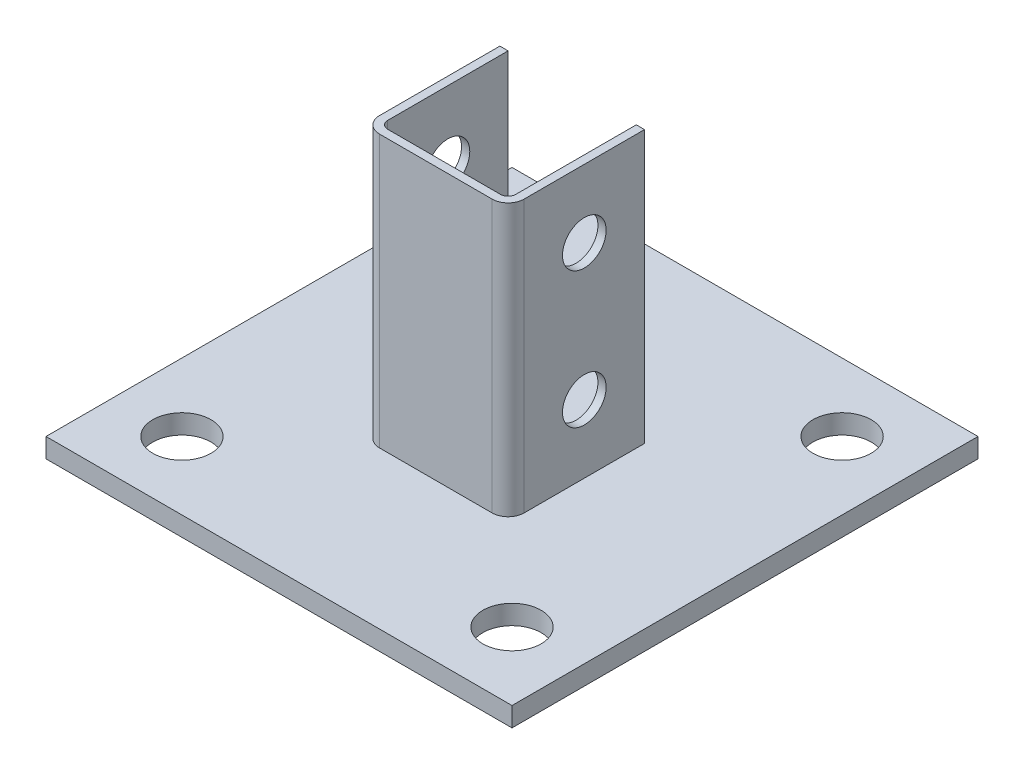
SolidWorks part; units mm, degrees
material "AISI Type 316L stainless steel"
ref_plane "Front Plane" through (0, 0, 0) normal (0, 0, 1) x (1, 0, 0)
ref_plane "Top Plane" through (0, 0, 0) normal (0, 1, 0) x (1, 0, 0)
ref_plane "Right Plane" through (0, 0, 0) normal (1, 0, 0) x (0, 0, -1)
ref_axis "X Axis" through (-125.9796, 0, 0) along (1, 0, 0)
ref_axis "Y Axis" through (0, -78.5041, 0) along (0, 1, 0)
ref_axis "Z Axis" through (0, 0, -88.99) along (0, 0, 1)
sketch "Sketch1" plane through (0, 0, 0) normal (0, 1, 0) x (1, 0, 0)
  line L1 (76.2, -76.2) -> (-76.2, -76.2)
  line L2 (76.2, -76.2) -> (76.2, 76.2)
  line L3 (76.2, 76.2) -> (-76.2, 76.2)
  line L4 (-76.2, -76.2) -> (-76.2, 76.2)
  line L5 (76.2, -76.2) -> (-76.2, 76.2) construction
  line L6 (76.2, 76.2) -> (-76.2, -76.2) construction
  point P0 (0, 0)
  dimension "D1" = 152.4
  dimension "D2" = 152.4
extrude "Extrude1" add sketch "Sketch1" along normal blind 6.35
hole_wizard "3/4 (0.75) Diameter Hole1" positions "Sketch3" profile "Sketch2" hole size "3/4" standard "Ansi Inch"
sketch "Sketch3" plane through (0, 6.35, 0) normal (0, 1, 0) x (-1, 0, 0)
  line L0 (53.975, -53.975) -> (-53.975, -53.975) construction
  line L1 (-53.975, -53.975) -> (-53.975, 53.975) construction
  line L2 (-53.975, 53.975) -> (53.975, 53.975) construction
  line L3 (53.975, 53.975) -> (53.975, -53.975) construction
  line L6 (-76.2, -76.2) -> (76.2, -76.2) construction
  line L7 (76.2, -76.2) -> (76.2, 76.2) construction
  line L8 (76.2, 76.2) -> (-76.2, 76.2) construction
  line L9 (-76.2, 76.2) -> (-76.2, -76.2) construction
  point P0 (53.975, -53.975)
  point P1 (-53.975, -53.975)
  point P3 (-53.975, 53.975)
  point P5 (53.975, 53.975)
  dimension "D1" = 22.225
  dimension "D2" = 22.225
  dimension "D3" = 22.225
  dimension "D4" = 22.225
sketch "Sketch2" plane through (-53.975, 6.35, -53.975) normal (1, 0, 0) x (0, 0, 1)
  line L0 (0, 0) -> (0, 118.4992)
  line L1 (0, 118.4992) -> (9.525, 112.776)
  line L2 (9.525, 112.776) -> (9.525, 0)
  line L5 (9.525, 0) -> (0, 0)
  line L10 (0, 118.4992) -> (-9.525, 112.776) construction
  line L11 (0, -6.35) -> (0, 107.95) construction
  dimension "Hole Dia." = 19.05
  dimension "Hole Depth" = 112.776
  dimension "Drill Angle" = 118
sketch "Sketch4" plane through (0, 6.35, 0) normal (0, 1, 0) x (1, 0, 0)
  line L0 (0, -76.2) -> (0, 76.2) construction
  line L1 (-76.2, -76.2) -> (76.2, -76.2) construction
  line L2 (76.2, 76.2) -> (-76.2, 76.2) construction
  line L3 (-76.2, 0) -> (76.2, 0) construction
  line L4 (-76.2, 76.2) -> (-76.2, -76.2) construction
  line L5 (76.2, -76.2) -> (76.2, 76.2) construction
  line L6 (-20.955, 19.685) -> (-20.955, -19.685)
  line L7 (-18.415, -22.225) -> (18.415, -22.225)
  line L8 (20.955, -19.685) -> (20.955, 19.685)
  arc A0 (-20.955, -19.685) -> (-18.415, -22.225) centre (-18.415, -19.685) ccw
  arc A1 (18.415, -22.225) -> (20.955, -19.685) centre (18.415, -19.685) ccw
  point P15 (-20.955, 0)
  point P17 (0, -22.225)
  point P20 (-20.955, -22.225)
  point P23 (20.955, -22.225)
  dimension "D3" = 2.54
  dimension "D1" = 41.91
  dimension "D2" = 41.91
extrude "Extrude-Thin1" add sketch "Sketch4" along normal blind 88.9 thin thin type one direction wall 2.6924
hole_wizard "9/16 (0.5625) Diameter Hole1" positions "Sketch6" profile "Sketch5" hole size "9/16" standard "Ansi Inch"
sketch "Sketch6" plane through (23.6474, 0, 0) normal (1, 0, 0) x (0, 0, -1)
  line L0 (0, 0) -> (0, 95.25) construction
  line L1 (-19.685, 95.25) -> (19.685, 95.25) construction
  line L4 (-19.685, 6.35) -> (19.685, 6.35) construction
  point P0 (0, 73.025)
  point P1 (0, 28.575)
  dimension "D1" = 22.225
  dimension "D2" = 22.225
sketch "Sketch5" plane through (23.6474, 73.025, 0) normal (0, 1, 0) x (0, 0, -1)
  line L0 (0, 0) -> (0, 117.0684)
  line L1 (0, 117.0684) -> (7.1437, 112.776)
  line L2 (7.1437, 112.776) -> (7.1437, 0)
  line L5 (7.1437, 0) -> (0, 0)
  line L10 (0, 117.0684) -> (-7.1438, 112.776) construction
  line L11 (0, -6.35) -> (0, 107.95) construction
  dimension "Hole Dia." = 14.2875
  dimension "Hole Depth" = 112.776
  dimension "Drill Angle" = 118
